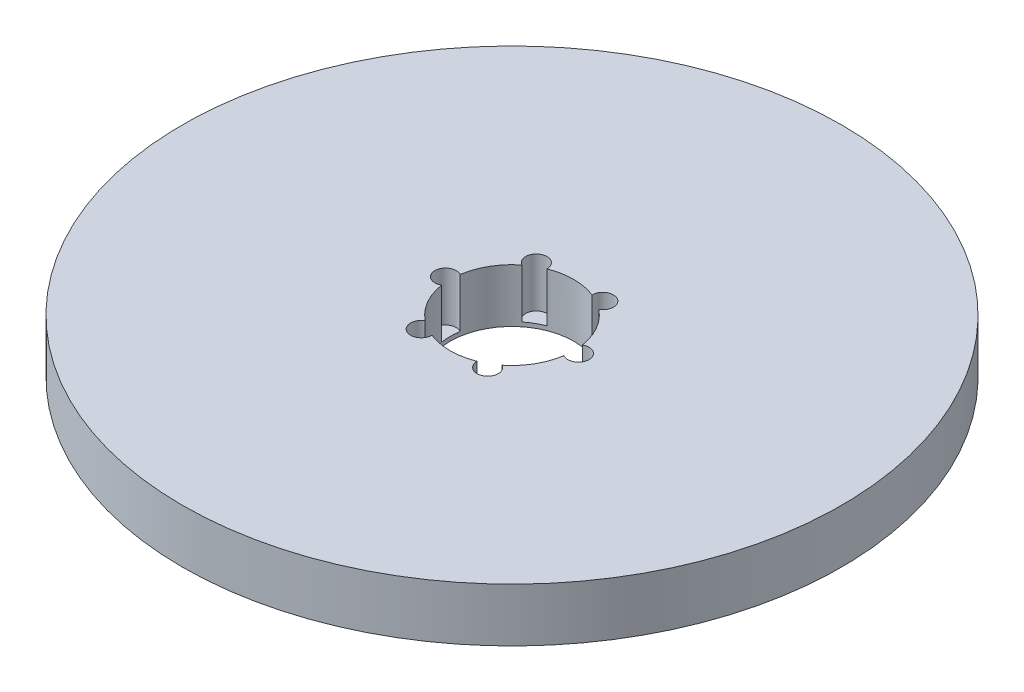
SolidWorks part; units mm, degrees
ref_plane "Front Plane" through (0, 0, 0) normal (0, 0, 1) x (1, 0, 0)
ref_plane "Top Plane" through (0, 0, 0) normal (0, 1, 0) x (1, 0, 0)
ref_plane "Right Plane" through (0, 0, 0) normal (1, 0, 0) x (0, 0, -1)
sketch "Sketch1" plane through (0, 0, 0) normal (0, 1, 0) x (1, 0, 0)
  circle A0 centre (0, 0) radius 80
  dimension "FLANGE_OD" = 160
extrude "Boss-Extrude1" add sketch "Sketch1" along normal blind 13
sketch "Sketch2" plane through (0, 0, 0) normal (0, 1, 0) x (1, 0, 0)
  circle A0 centre (0, 0) radius 15
  dimension "BORE_D" = 30
extrude "Cut-Extrude1" cut sketch "Sketch2" along normal through all
sketch "Sketch3" plane through (0, 13, 0) normal (0, 1, 0) x (1, 0, 0)
  circle A0 centre (0, 0) radius 16.131 construction
  circle A1 centre (-16.131, 0) radius 2.5863
  dimension "BOLT_D" = 5.1725
  dimension "BOLT_PCD" = 32.2619
extrude "Cut-Extrude2" cut sketch "Sketch3" against normal blind 11.9797
pattern_circular "CirPattern1" count 6 over 360 about axis through (0, 0, 0) along (0, 1, 0) of "Cut-Extrude2"
